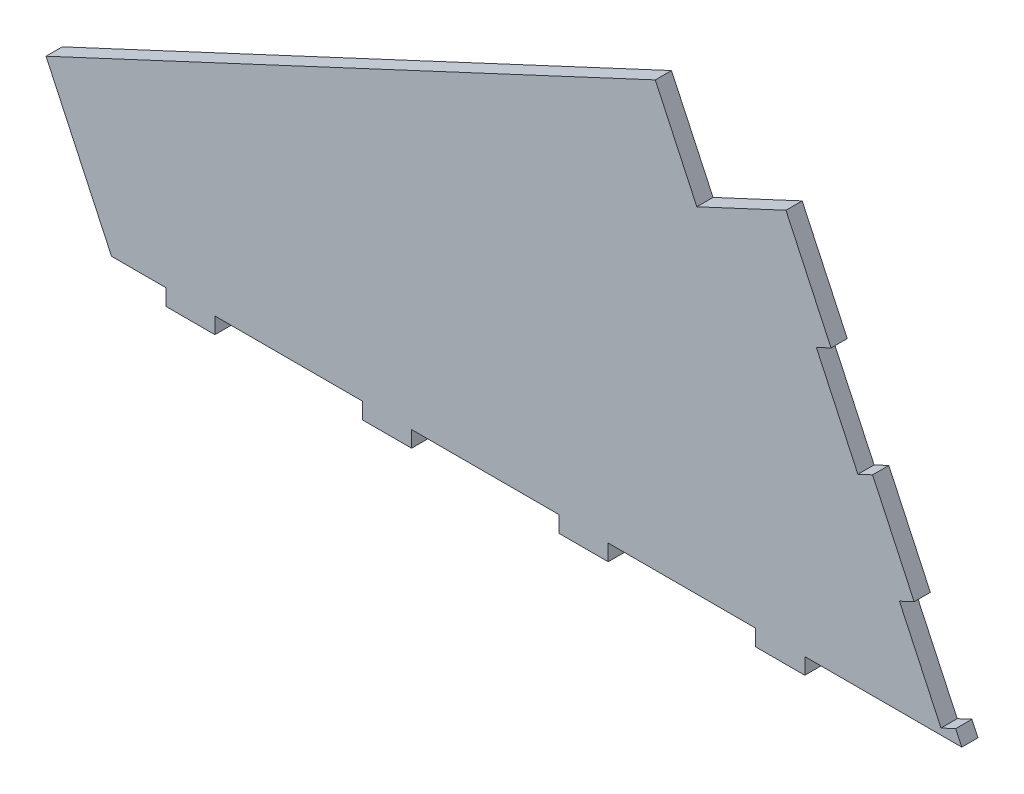
SolidWorks part; units mm, degrees
material "Balsa"
ref_plane "Front Plane" through (0, 0, 0) normal (0, 0, 1) x (1, 0, 0)
ref_plane "Top Plane" through (0, 0, 0) normal (0, 1, 0) x (1, 0, 0)
ref_plane "Right Plane" through (0, 0, 0) normal (1, 0, 0) x (0, 0, -1)
sketch "Sketch1" plane through (0, 0, 0) normal (0, 0, 1) x (1, 0, 0)
  line L0 (321.5462, 12.6346) -> (148.586, 12.6346)
  line L1 (148.586, 12.6346) -> (135.2566, 41.2196)
  line L2 (135.2566, 41.2196) -> (259.1989, 99.0148)
  line L3 (-63.4467, -51.4373) -> (255.5737, 97.3243) construction
  line L4 (259.1989, 99.0148) -> (267.6513, 80.8887)
  line L5 (267.6513, 80.8887) -> (285.7774, 89.341)
  line L6 (285.7774, 89.341) -> (321.5462, 12.6346)
  line L7 (327.4362, 0.0035) -> (398.701, -152.8244) construction
  line L9 (285.7774, 89.341) -> (294.9517, 69.6668) construction
  line L11 (135.2566, 41.2196) -> (148.586, 12.6346) construction
  line L12 (174.6178, 12.6346) -> (194.6178, 12.6346) construction
  dimension "D1" = 20
  dimension "D2" = 20
extrude "Boss-Extrude1" add sketch "Sketch1" against normal blind 3.3
sketch "Sketch2" plane through (0, 0, 0) normal (0, 0, 1) x (1, 0, 0)
  line L0 (303.404, 51.5407) -> (294.9517, 69.6668)
  line L1 (303.404, 51.5407) -> (300.4132, 50.146)
  line L2 (294.9517, 69.6668) -> (291.9609, 68.2722)
  line L3 (300.4132, 50.146) -> (291.9609, 68.2722)
  line L4 (320.3088, 15.2883) -> (311.8564, 33.4145)
  line L5 (320.3088, 15.2883) -> (317.3179, 13.8937)
  line L6 (311.8564, 33.4145) -> (308.8656, 32.0199)
  line L7 (317.3179, 13.8937) -> (308.8656, 32.0199)
  dimension "D1" = 3.3
  dimension "D2" = 3.3
extrude "Cut-Extrude1" cut sketch "Sketch2" against normal blind 3.3
sketch "Sketch3" plane through (0, 0, 0) normal (0, 0, 1) x (1, 0, 0)
  line L0 (289.6178, 9.3346) -> (279.6178, 9.3346)
  line L1 (289.6178, 9.3346) -> (289.6178, 13.052)
  line L2 (279.6178, 9.3346) -> (279.6178, 13.052)
  line L3 (289.6178, 13.052) -> (279.6178, 13.052)
  line L4 (249.6178, 9.3346) -> (239.6178, 9.3346)
  line L5 (249.6178, 9.3346) -> (249.6178, 12.9084)
  line L6 (239.6178, 9.3346) -> (239.6178, 12.9084)
  line L7 (249.6178, 12.9084) -> (239.6178, 12.9084)
  line L8 (209.6178, 9.3346) -> (199.6178, 9.3346)
  line L9 (209.6178, 9.3346) -> (209.6178, 13.0454)
  line L10 (199.6178, 9.3346) -> (199.6178, 13.0454)
  line L11 (209.6178, 13.0454) -> (199.6178, 13.0454)
  line L12 (169.6178, 9.3346) -> (159.6178, 9.3346)
  line L13 (169.6178, 9.3346) -> (169.6178, 12.8442)
  line L14 (159.6178, 9.3346) -> (159.6178, 12.8442)
  line L15 (169.6178, 12.8442) -> (159.6178, 12.8442)
extrude "Boss-Extrude2" add sketch "Sketch3" against normal blind 3.3
